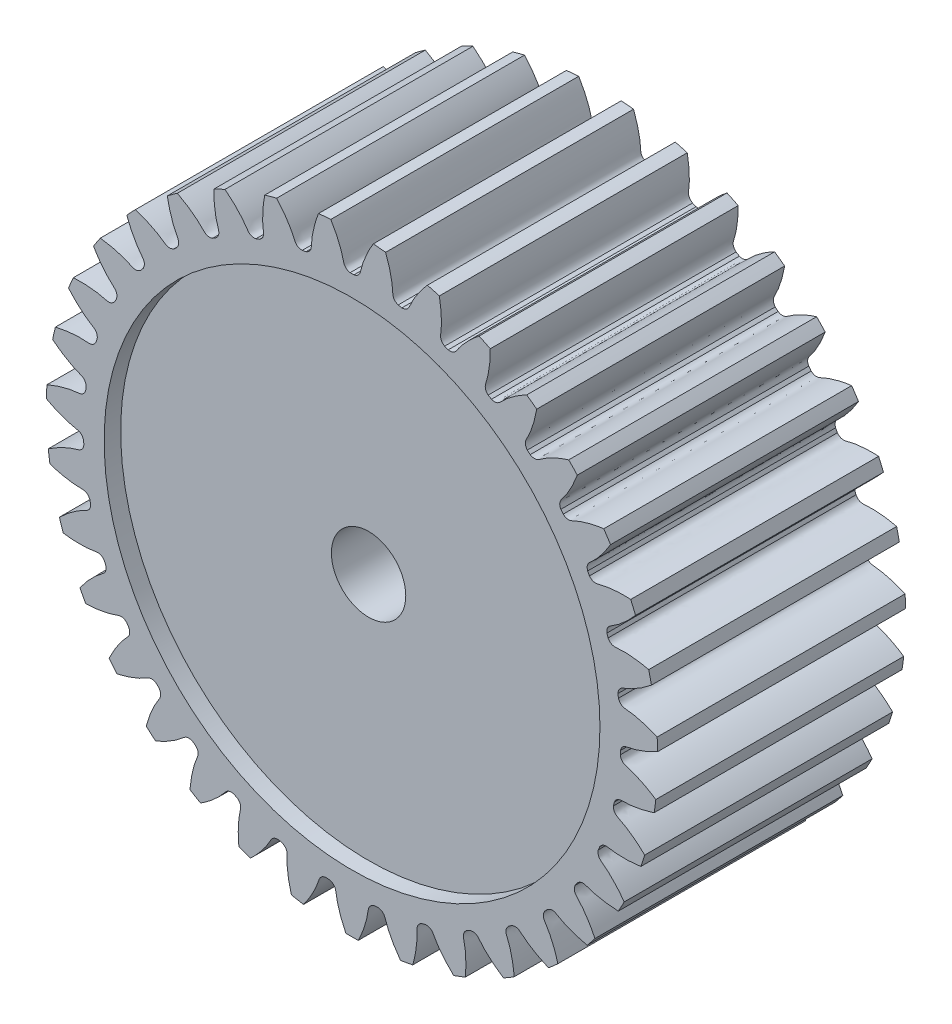
SolidWorks part; units mm, degrees
ref_plane "前视基准面" through (0, 0, 0) normal (0, 0, 1) x (1, 0, 0)
ref_plane "上视基准面" through (0, 0, 0) normal (0, 1, 0) x (1, 0, 0)
ref_plane "右视基准面" through (0, 0, 0) normal (1, 0, 0) x (0, 0, -1)
sketch "草图1" plane through (0, 0, 0) normal (0, 0, 1) x (1, 0, 0)
  circle A0 centre (0, 0) radius 37
extrude "凸台-拉伸1" add sketch "草图1" along normal blind 30
ref_axis "基准轴1" through (0, 0, 30) along (0, 0, -1)
sketch "草图2" plane through (0, 0, 0) normal (0, 0, 1) x (1, 0, 0)
  line L0 (0, 0) -> (0, 37) construction
  circle A0 centre (0, 0) radius 37 construction
  arc A1 (0.2321, 32.4992) -> (-0.2321, 32.4992) centre (0, 0) ccw
  arc A2 (7.1029, 42.1361) -> (-7.1029, 42.1361) centre (0, 0) ccw
  spline S0 degree 3 poles (0.2321, 32.4992) (0.9482, 32.6535) (1.0024, 33.1766) (1.1442, 33.7289) (1.1861, 33.8807) (1.2349, 34.0443) (1.291, 34.2194) (1.3548, 34.4057) (1.4268, 34.6031) (1.5075, 34.8114) (1.5973, 35.0301) (1.6967, 35.259) (1.8062, 35.4979) (1.9261, 35.7464) (2.057, 36.0042) (2.1991, 36.2709) (2.353, 36.5462) (2.519, 36.8297) (2.6975, 37.1211) (2.8889, 37.4199) (3.0935, 37.7258) (3.3117, 38.0383) (3.5439, 38.3571) (3.7904, 38.6816) (4.0515, 39.0114) (4.3275, 39.346) (4.6187, 39.6851) (4.9254, 40.0281) (5.2478, 40.3745) (5.5863, 40.7239) (5.941, 41.0757) (6.4423, 41.5533) (6.834, 41.9044) (7.1029, 42.1361) knots 0 0 0 0 0.117409 0.129436 0.142561 0.156781 0.172098 0.18851 0.206019 0.224624 0.244325 0.265123 0.287016 0.310006 0.334092 0.359274 0.385553 0.412927 0.441398 0.470965 0.501628 0.533387 0.566243 0.600194 0.635242 0.671386 0.708626 0.746962 0.786395 0.826923 0.868548 0.911269 1 1 1 1
  spline S1 degree 3 poles (-0.2321, 32.4992) (-0.9482, 32.6535) (-1.0024, 33.1766) (-1.1442, 33.7289) (-1.1861, 33.8807) (-1.2349, 34.0443) (-1.291, 34.2194) (-1.3548, 34.4057) (-1.4268, 34.6031) (-1.5075, 34.8114) (-1.5973, 35.0301) (-1.6967, 35.259) (-1.8062, 35.4979) (-1.9261, 35.7464) (-2.057, 36.0042) (-2.1991, 36.2709) (-2.353, 36.5462) (-2.519, 36.8297) (-2.6975, 37.1211) (-2.8889, 37.4199) (-3.0935, 37.7258) (-3.3117, 38.0383) (-3.5439, 38.3571) (-3.7904, 38.6816) (-4.0515, 39.0114) (-4.3275, 39.346) (-4.6187, 39.6851) (-4.9254, 40.0281) (-5.2478, 40.3745) (-5.5863, 40.7239) (-5.941, 41.0757) (-6.4423, 41.5533) (-6.834, 41.9044) (-7.1029, 42.1361) knots 0 0 0 0 0.117409 0.129436 0.142561 0.156781 0.172098 0.18851 0.206019 0.224624 0.244325 0.265123 0.287016 0.310006 0.334092 0.359274 0.385553 0.412927 0.441398 0.470965 0.501628 0.533387 0.566243 0.600194 0.635242 0.671386 0.708626 0.746962 0.786395 0.826923 0.868548 0.911269 1 1 1 1
extrude "切除-拉伸1" cut sketch "草图2" along normal through all
pattern_circular "阵列(圆周)1" count 35 every 10.286 about axis through (0, 0, 30) along (0, 0, -1) of "切除-拉伸1"
sketch "草图3" plane through (0, 0, 0) normal (0, 0, 1) x (1, 0, 0)
  circle A0 centre (0, 0) radius 35 construction
  dimension "Dn" = 70
sketch "草图4" plane through (0, 0, 30) normal (0, 0, 1) x (1, 0, 0)
  circle A0 centre (0, 0) radius 4.5
  dimension "D1" = 9
extrude "切除-拉伸2" cut sketch "草图4" against normal through all
sketch "草图5" plane through (0, 0, 30) normal (0, 0, 1) x (1, 0, 0)
  circle A0 centre (0, 0) radius 30
  dimension "D1" = 60
extrude "切除-拉伸3" cut sketch "草图5" against normal blind 2
sketch "草图6" plane through (0, 0, 0) normal (0, 0, -1) x (-1, 0, 0)
  circle A0 centre (0, 0) radius 30
  dimension "D1" = 60
extrude "切除-拉伸4" cut sketch "草图6" against normal blind 2
